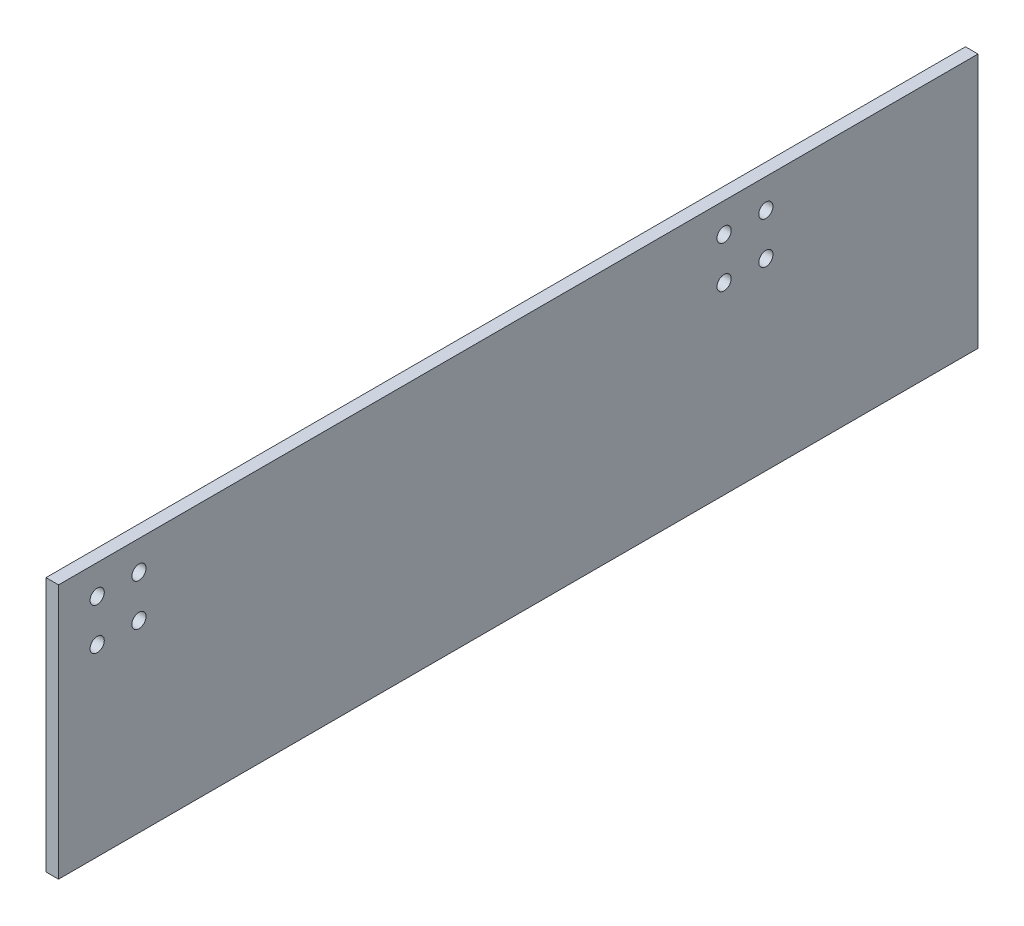
SolidWorks part; units mm, degrees
ref_plane "Front Plane" through (0, 0, 0) normal (0, 0, 1) x (1, 0, 0)
ref_plane "Top Plane" through (0, 0, 0) normal (0, 1, 0) x (1, 0, 0)
ref_plane "Right Plane" through (0, 0, 0) normal (1, 0, 0) x (0, 0, -1)
sketch "Sketch1" plane through (0, 0, 0) normal (0, 0, 1) x (1, 0, 0)
  line L0 (3, 76) -> (3, 0)
  line L2 (0, 0) -> (0, 76)
  line L5 (3, 0) -> (0, 0)
  line L6 (3, 76) -> (0, 76)
  dimension "D1" = 76
  dimension "D2" = 3
extrude "Boss-Extrude1" add sketch "Sketch1" along normal blind 220 contours L2 L0 region at (1.5, 38, 0)
hole_wizard "M3 Clearance Hole1" positions "Sketch2" profile "Sketch3" hole size "M3" standard "ANSI Metric" end condition through all
sketch "Sketch2" plane through (0, 0, 0) normal (-1, 0, 0) x (0, 0, 1)
  point P0 (50.7547, 59)
  point P3 (60.7547, 59)
  point P6 (60.7547, 69)
  point P9 (50.7547, 69)
  point P12 (200.7547, 59)
  point P15 (200.7547, 69)
  point P18 (210.7547, 59)
  point P21 (210.7547, 69)
sketch "Sketch3" plane through (0, 59, 50.7547) normal (0, 1, 0) x (0, 0, 1)
  line L0 (0, 0) -> (0, 3)
  line L1 (0, 3) -> (1.7, 3)
  line L2 (1.7, 3) -> (1.7, 0.025)
  line L3 (1.7, 0.025) -> (1.725, 0)
  line L5 (1.725, 0) -> (0, 0)
  line L6 (-1.7, 0.025) -> (-1.725, 0) construction
  line L11 (0, -6.35) -> (0, 107.95) construction
  dimension "Thru Hole Dia." = 3.4
  dimension "Thru Hole Depth" = 3
  dimension "Near C'Sink Dia." = 3.45
  dimension "Near C'Sink Angle" = 90
sketch "Sketch4" plane through (0, 0, 0) normal (-1, 0, 0) x (0, 0, 1)
  line L0 (220, 0) -> (220, 76) construction
  line L1 (0, 0) -> (220, 0)
  line L2 (0, 0) -> (0, 15)
  line L3 (0, 15) -> (220, 15)
  line L4 (220, 0) -> (220, 15)
  dimension "D1" = 15
extrude "Cut-Extrude1" cut sketch "Sketch4" against normal through all
